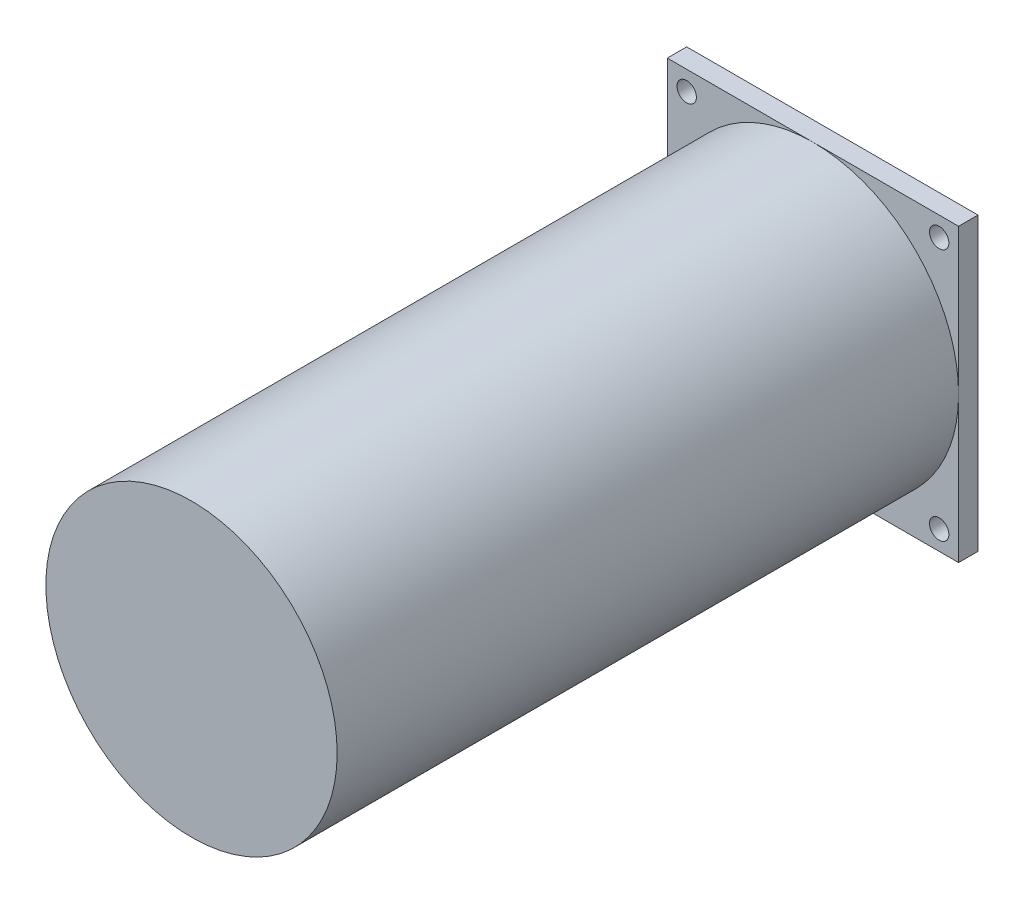
SolidWorks part; units mm, degrees
material "AISI 4340 Stahllegierung"
ref_plane "Ebene vorne" through (0, 0, 0) normal (0, 0, 1) x (1, 0, 0)
ref_plane "Ebene oben" through (0, 0, 0) normal (0, 1, 0) x (1, 0, 0)
ref_plane "Ebene rechts" through (0, 0, 0) normal (1, 0, 0) x (0, 0, -1)
sketch "Skizze2" plane through (0, 0, 0) normal (0, 0, 1) x (1, 0, 0)
  line L1 (-75, 75) -> (75, 75)
  line L2 (-75, 75) -> (-75, -75)
  line L3 (-75, -75) -> (75, -75)
  line L4 (75, 75) -> (75, -75)
  line L5 (-75, 75) -> (75, -75) construction
  line L6 (-75, -75) -> (75, 75) construction
  circle A0 centre (-65, 65) radius 5
  circle A1 centre (65, 65) radius 5
  circle A2 centre (65, -65) radius 5
  circle A3 centre (-65, -65) radius 5
  point P0 (0, 0)
  dimension "D3" = 10
  dimension "D1" = 150
  dimension "D2" = 150
  dimension "D4" = 10
extrude "Aufsatz-Linear austragen1" add sketch "Skizze2" along normal blind 10
sketch "Skizze3" plane through (0, 0, 10) normal (0, 0, 1) x (1, 0, 0)
  circle A0 centre (0, 0) radius 75
extrude "Aufsatz-Linear austragen2" add sketch "Skizze3" along normal blind 320
ref_axis "Verbindung_base" through (0, 0, -18) along (0, 0, 1)
